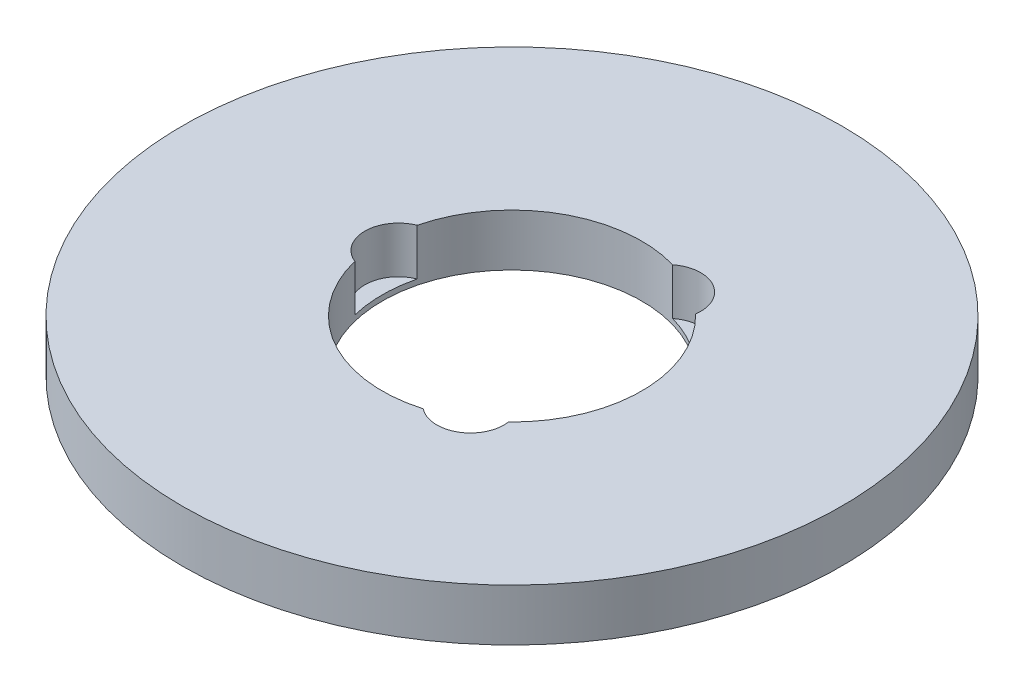
SolidWorks part; units mm, degrees
ref_plane "Front Plane" through (0, 0, 0) normal (0, 0, 1) x (1, 0, 0)
ref_plane "Top Plane" through (0, 0, 0) normal (0, 1, 0) x (1, 0, 0)
ref_plane "Right Plane" through (0, 0, 0) normal (1, 0, 0) x (0, 0, -1)
sketch "Sketch1" plane through (0, 0, 0) normal (0, 1, 0) x (1, 0, 0)
  circle A0 centre (0, 0) radius 82.5
  dimension "FLANGE_OD" = 165
extrude "Boss-Extrude1" add sketch "Sketch1" along normal blind 13
sketch "Sketch2" plane through (0, 0, 0) normal (0, 1, 0) x (1, 0, 0)
  circle A0 centre (0, 0) radius 32.5
  dimension "BORE_D" = 65
extrude "Cut-Extrude1" cut sketch "Sketch2" along normal through all
sketch "Sketch3" plane through (0, 13, 0) normal (0, 1, 0) x (1, 0, 0)
  circle A0 centre (0, 0) radius 28.4265 construction
  circle A1 centre (-28.4265, 0) radius 8.4118
  dimension "BOLT_D" = 16.8237
  dimension "BOLT_PCD" = 56.8529
extrude "Cut-Extrude2" cut sketch "Sketch3" against normal blind 11.6518
pattern_circular "CirPattern1" count 3 over 360 about axis through (0, 0, 0) along (0, 1, 0) of "Cut-Extrude2"
